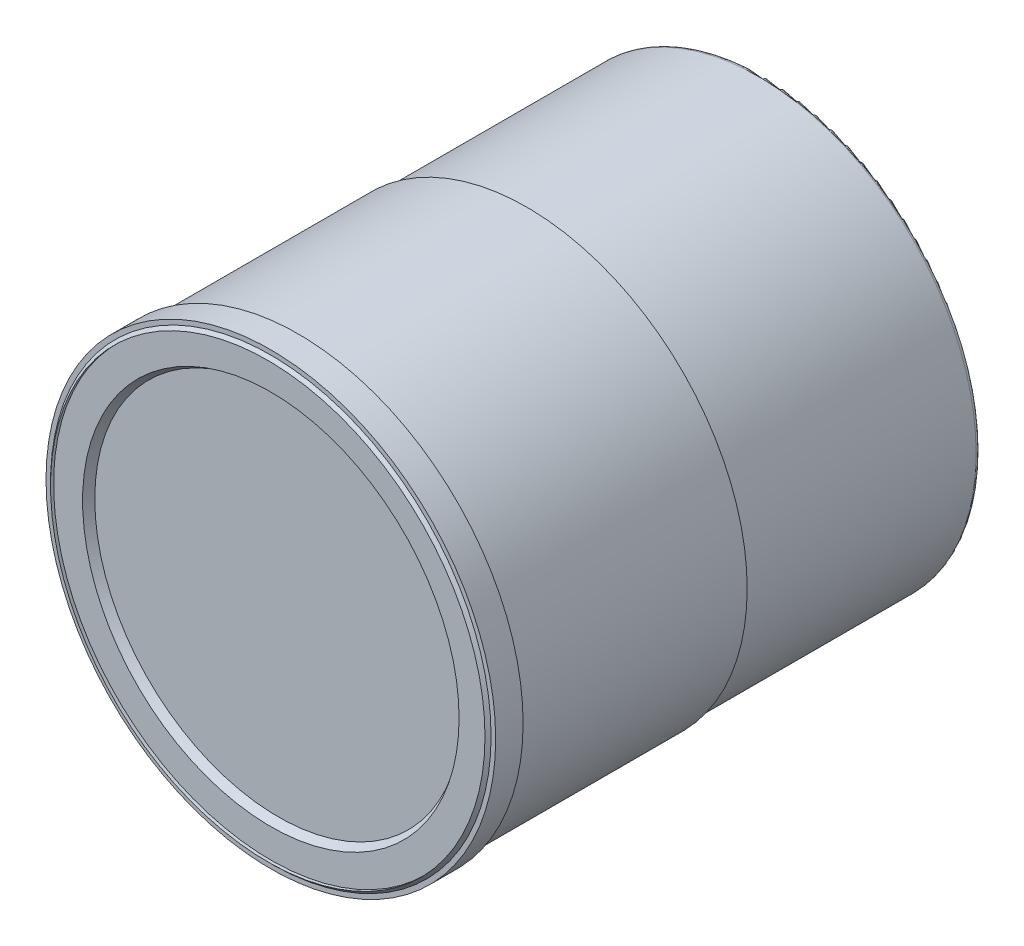
SolidWorks part; units mm, degrees
material "ABS"
ref_plane "Front Plane" through (0, 0, 0) normal (1, 0, 0) x (0, 1, 0)
ref_plane "Top Plane" through (0, 0, 0) normal (0, 0, 1) x (0, 1, 0)
ref_plane "Right Plane" through (0, 0, 0) normal (0, 1, 0) x (-1, 0, 0)
sketch "Sketch1" plane through (0, 0, 0) normal (0, 0, 1) x (0, 1, 0)
  circle A0 centre (0, 0) radius 46.25
  circle A1 centre (0, 0) radius 71.25
  dimension "D1" = 92.5
  dimension "D2" = 25
extrude "Boss-Extrude1" add sketch "Sketch1" along normal blind 77.6 contours A1
sketch "Sketch2" plane through (0, 0, 77.6) normal (0, 0, 1) x (1, 0, 0)
  circle A0 centre (0, 0) radius 72.25
  circle A1 centre (0, 0) radius 71.25 construction
  dimension "D1" = 1
extrude "Boss-Extrude2" add sketch "Sketch2" along normal blind 82.5
extrude "Cut-Extrude1" cut sketch "Sketch1<3>" along normal blind 100.7 contours A0
sketch "Sketch1<3>" plane through (0, 0, 0) normal (0, 0, 1) x (0, 1, 0) same geometry as "Sketch1"
fillet "Fillet1" radius 1.5 3 edges at (71.25, 0, 0) (46.25, 0, 0) (46.25, 0, 100.7)
sketch "Sketch3" plane through (0, 0, 160.1) normal (0, 0, 1) x (1, 0, 0)
  circle A0 centre (0, 0) radius 73.75
  circle A1 centre (0, 0) radius 72.25 construction
  dimension "D1" = 1.5
extrude "Boss-Extrude3" add sketch "Sketch3" against normal blind 7.5 and the other way blind 1.5 contours A0
sketch "Sketch4" plane through (0, 0, 161.6) normal (0, 0, 1) x (1, 0, 0)
  circle A0 centre (0, 0) radius 72.25
  circle A1 centre (0, 0) radius 71.25
  circle A2 centre (0, 0) radius 73.75 construction
  dimension "D1" = 1
  dimension "D2" = 2.5
extrude "Boss-Extrude4" add sketch "Sketch4" along normal blind 1 contours A0 | A1
chamfer "Chamfer1" distance 1 angle 45 1 edges at (72.25, 0, 162.6)
sketch "Sketch5" plane through (0, 0, 161.6) normal (0, 0, 1) x (1, 0, 0)
  circle A0 centre (0, 0) radius 60.25
  circle A1 centre (0, 0) radius 73.75 construction
  dimension "D1" = 13.5
extrude "Cut-Extrude2" cut sketch "Sketch5" against normal blind 2.5
chamfer "Chamfer2" distance 1.5 distance2 2.5 1 edges at (60.25, 0, 161.6) first distance on face at (60.25, 0, 161.6)
equation "\"D1@Boss-Extrude3\"=9mm-1.5mm"
